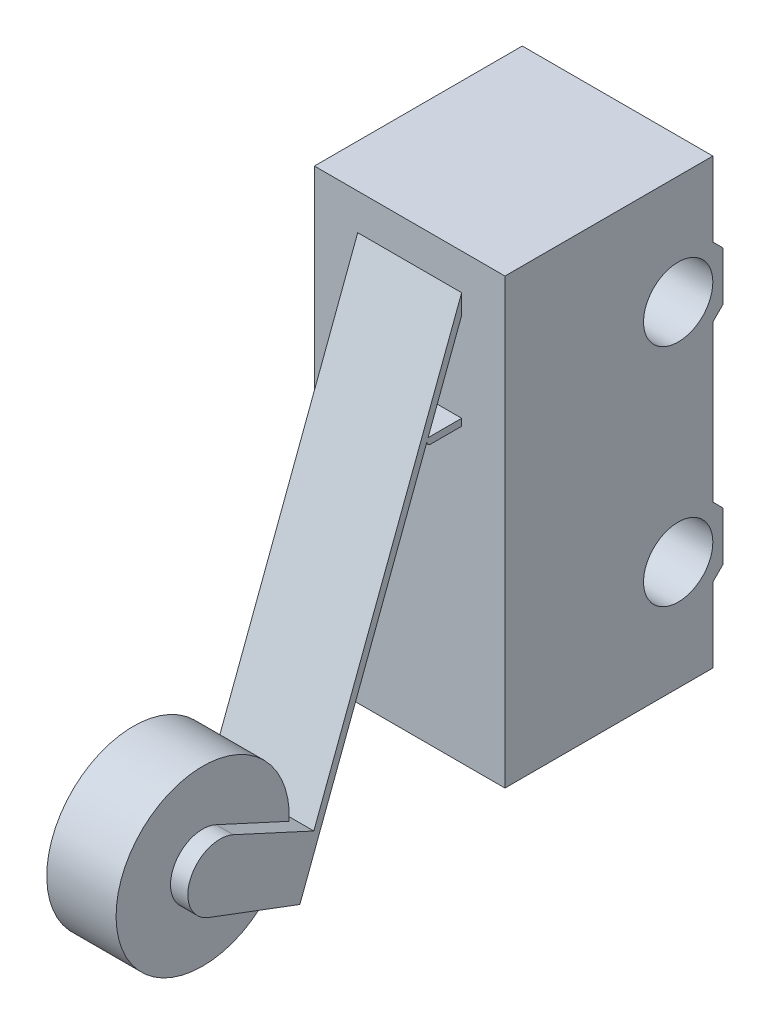
SolidWorks part; units mm, degrees
ref_plane "前视基准面" through (0, 0, 0) normal (0, 0, 1) x (1, 0, 0)
ref_plane "上视基准面" through (0, 0, 0) normal (0, 1, 0) x (1, 0, 0)
ref_plane "右视基准面" through (0, 0, 0) normal (1, 0, 0) x (0, 0, -1)
sketch "草图1" plane through (0, 0, 0) normal (1, 0, 0) x (0, 0, -1)
  line L0 (0, -6.4) -> (6, -6.4) construction
  line L1 (0, 0) -> (6, 0)
  line L2 (0, 0) -> (0, -12.8)
  line L3 (0, -12.8) -> (6, -12.8)
  line L4 (6, 0) -> (6, -2.15)
  line L5 (6, -2.15) -> (6.3, -2.45)
  line L6 (6.3, -2.45) -> (6.3, -3.85)
  line L7 (6.3, -3.85) -> (6, -4.15)
  line L8 (5, -2.15) -> (2.5627, -2.15) construction
  line L9 (5, -4.15) -> (2.0811, -4.15) construction
  line L10 (5, -8.65) -> (2.9876, -8.65) construction
  line L11 (6, -4.15) -> (6, -8.65)
  line L12 (2.9876, -10.65) -> (5, -10.65) construction
  line L13 (6.3, -8.95) -> (6, -8.65)
  line L14 (6.3, -10.35) -> (6.3, -8.95)
  line L15 (6, -10.65) -> (6.3, -10.35)
  line L16 (6, -10.65) -> (6, -12.8)
  circle A0 centre (5, -3.15) radius 1
  circle A1 centre (5, -9.65) radius 1
  point P27 (6.3, -3.15)
  dimension "D3" = 2
  dimension "D1" = 12.8
  dimension "D2" = 6
  dimension "D4" = 5
  dimension "D5" = 6.5
  dimension "D6" = 0.3
  dimension "D7" = 1.4
extrude "凸台-拉伸2" add sketch "草图1" along normal blind 2.75 and the other way blind 2.75
sketch "草图2" plane through (0, 0, 0) normal (1, 0, 0) x (0, 0, -1)
  line L0 (0, 0) -> (0, -12.8) construction
  line L1 (0.1872, -1.1117) -> (-0.9692, -4.18)
  line L2 (-4.67, -14) -> (-4.8571, -13.9295)
  line L3 (-4.2669, -12.3633) -> (0, -1.0412)
  line L4 (0, -1.0412) -> (0.1872, -1.1117)
  line L5 (6, 0) -> (0, 0) construction
  line L7 (0, -4.38) -> (0, -4.18)
  line L11 (-1.0423, -4.374) -> (-4.67, -14)
  line L12 (0, -4.18) -> (-0.9, -4.18)
  line L13 (-0.9, -4.38) -> (0, -4.38)
  line L14 (-1, -4.28) -> (-1, -5.1697) construction
  line L15 (6.3, -3.85) -> (6.3, -2.45) construction
  line L16 (-9.38, -7.1099) -> (-9.38, -12.1396) construction
  line L17 (6.3, -10.35) -> (6.3, -8.95) construction
  line L18 (-4.8571, -13.9295) -> (-7.3024, -13.0079)
  line L19 (-6.5875, -11.2965) -> (-4.2669, -12.3633)
  line L20 (-0.9, -4.18) -> (-0.9692, -4.18)
  line L21 (-0.9936, -4.2447) -> (-1.0423, -4.374)
  arc A0 (-0.9936, -4.2447) -> (-0.9, -4.38) centre (-0.9, -4.28) ccw
  circle A1 centre (-6.9751, -12.1396) radius 2.4049 construction
  arc A2 (-6.5875, -11.2965) -> (-7.3024, -13.0079) centre (-6.9751, -12.1396) ccw
  point P11 (0, -4.28)
  point P31 (0, 0)
  dimension "D2" = 0.2
  dimension "D3" = 0.2
  dimension "D1" = 4.28
  dimension "D4" = 7.3
  dimension "D5" = 14
  dimension "D6" = 15.68
extrude "凸台-拉伸3" add sketch "草图2" along normal blind 1.5 and the other way blind 1.5
sketch "草图3" plane through (0, 0, 0) normal (1, 0, 0) x (0, 0, -1)
  circle A0 centre (-6.9751, -12.1396) radius 2.5
  dimension "D1" = 5
extrude "凸台-拉伸4" add sketch "草图3" along normal mid plane 2
